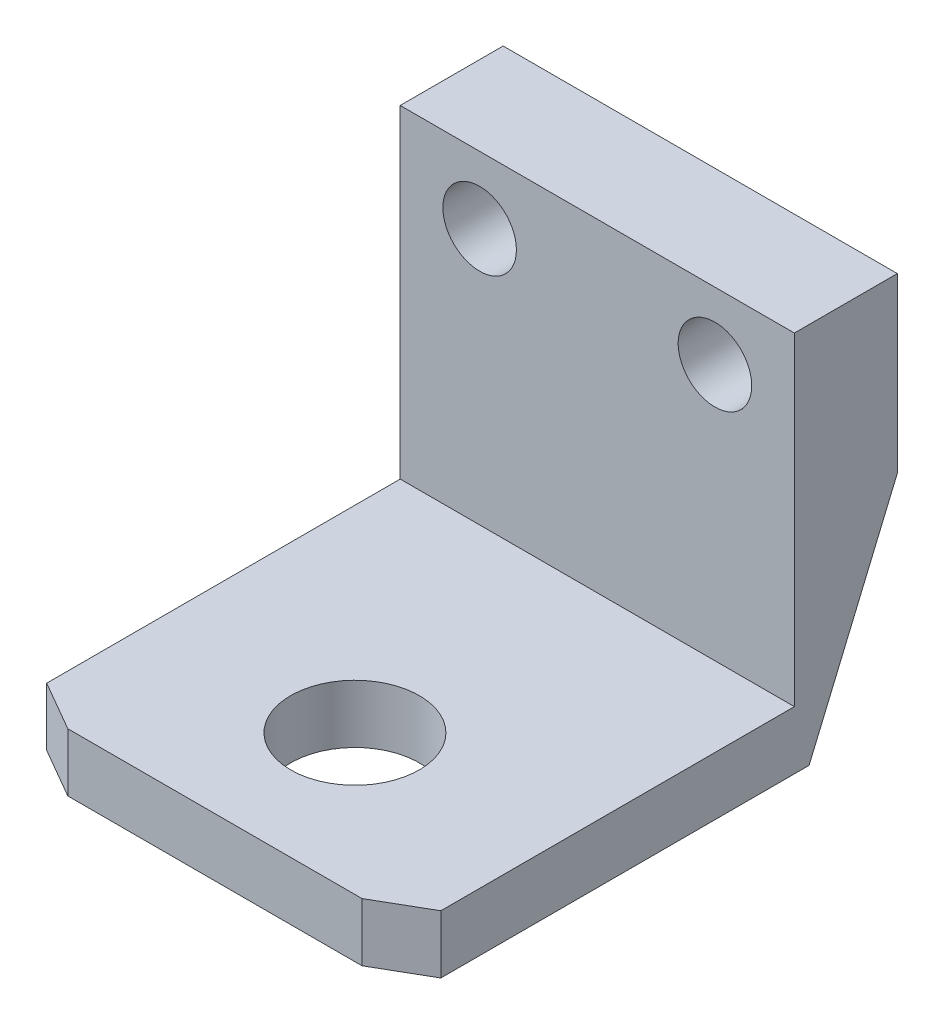
SolidWorks part; units mm, degrees
ref_plane "Front Plane" through (0, 0, 0) normal (0, 0, 1) x (1, 0, 0)
ref_plane "Top Plane" through (0, 0, 0) normal (0, 1, 0) x (1, 0, 0)
ref_plane "Right Plane" through (0, 0, 0) normal (1, 0, 0) x (0, 0, -1)
sketch "Sketch1" plane through (0, 0, 0) normal (0, 1, 0) x (1, 0, 0)
  line L0 (-27.051, 7.874) -> (-17.018, 7.874)
  line L1 (27.051, 7.874) -> (27.051, -7.874)
  line L2 (27.051, -7.874) -> (12.7, -16.1596)
  line L3 (12.7, -16.1596) -> (-12.7, -16.1596)
  line L4 (-12.7, -16.1596) -> (-27.051, -7.874)
  line L5 (-27.051, -7.874) -> (-27.051, 7.874)
  line L6 (-17.018, 7.874) -> (-17.018, 16.8604)
  line L7 (-17.018, 16.8604) -> (17.018, 16.8604)
  line L8 (17.018, 16.8604) -> (17.018, 7.874)
  line L9 (17.018, 7.874) -> (27.051, 7.874)
  line L10 (0, -55) -> (0, 55) construction
  line L11 (-27.051, 0) -> (27.051, 0) construction
  line L14 (-55, 0) -> (55, 0) construction
  point P2 (0, -16.1596)
  point P13 (0, 16.8604)
  point P14 (0, 0)
  dimension "D1" = 25.4
  dimension "D3" = 54.102
  dimension "D4" = 34.036
  dimension "D5" = 33.02
  dimension "D2" = 15.748
  dimension "D6" = 30
extrude "Boss-Extrude1" add sketch "Sketch1" along normal blind 5.0292 contours L0 L6 L7 L8 L9 L1 L2 L3 L4 L5
sketch "Sketch2" plane through (0, 0, 0) normal (0, 1, 0) x (1, 0, 0)
  line L0 (0, -55) -> (0, 55) construction
  line L1 (17.018, 25.7504) -> (-17.018, 25.7504)
  line L2 (17.018, 25.7504) -> (17.018, 16.8604)
  line L3 (17.018, 16.8604) -> (-17.018, 16.8604)
  line L4 (-17.018, 25.7504) -> (-17.018, 16.8604)
  line L5 (17.018, 25.7504) -> (-17.018, 16.8604) construction
  line L6 (17.018, 16.8604) -> (-17.018, 25.7504) construction
  point P0 (0, 21.3054)
  dimension "D1" = 8.89
extrude "Boss-Extrude2" add sketch "Sketch2" along normal blind 32.9692
sketch "Sketch3" plane through (17.018, 0, 0) normal (1, 0, 0) x (0, 0, -1)
  line L0 (25.7504, 32.9692) -> (25.7504, 0) construction
  line L1 (16.8604, 32.9692) -> (25.7504, 32.9692) construction
  line L2 (55, 0) -> (-55, 0) construction
  line L3 (25.7504, 18.034) -> (18.1304, 0)
  point P0 (25.7504, 18.034)
  point P5 (18.1304, 0)
  dimension "D1" = 14.9352
  dimension "D2" = 7.62
extrude "Cut-Extrude1" cut sketch "Sketch3" against normal through all and the other way through all
sketch "Sketch4" plane through (0, 0, -16.8604) normal (0, 0, 1) x (1, 0, 0)
  line L0 (-10.16, 27.178) -> (10.16, 27.178)
  line L1 (0, -18.1331) -> (0, 18.1331) construction
  line L2 (-17.018, 32.9692) -> (17.018, 32.9692) construction
  point P0 (-10.16, 27.178)
  point P1 (10.16, 27.178)
  point P2 (0, 27.178)
  dimension "D1" = 20.32
  dimension "D2" = 5.7912
hole_wizard "1/4 (0.25) Diameter Hole1" positions "Sketch5" profile "Sketch6" hole size "1/4" standard "ANSI Inch" end condition through all
sketch "Sketch5" plane through (0, 0, -16.8604) normal (0, 0, 1) x (1, 0, 0)
  point P0 (-10.16, 27.178)
  point P3 (10.16, 27.178)
sketch "Sketch6" plane through (-10.16, 27.178, -16.8604) normal (1, 0, 0) x (0, -1, 0)
  line L0 (0, 0) -> (0, 8.89)
  line L1 (0, 8.89) -> (3.175, 8.89)
  line L2 (3.175, 8.89) -> (3.175, 0)
  line L5 (3.175, 0) -> (0, 0)
  line L11 (0, -6.35) -> (0, 107.95) construction
  dimension "Thru Hole Dia." = 6.35
  dimension "Thru Hole Depth" = 8.89
sketch "Sketch7" plane through (0, 5.0292, 0) normal (0, 1, 0) x (1, 0, 0)
  line L0 (0, -18.1331) -> (0, 18.1331) construction
  line L1 (-27.051, -7.874) -> (-27.051, 7.874) construction
  circle A0 centre (0, -4.064) radius 5.5562
  point P0 (0, -4.064)
  point P5 (-27.051, -4.064)
  dimension "D1" = 11.1125
  dimension "D2" = 3.81
extrude "Cut-Extrude2" cut sketch "Sketch7" against normal through all contours A0
sketch "Sketch8" plane through (0, 5.0292, 0) normal (0, 1, 0) x (1, 0, 0)
  line L0 (27.051, 7.874) -> (27.051, -7.874) construction
  line L1 (-27.051, -7.874) -> (-27.051, 7.874) construction
  point P0 (23.241, -4.064)
  point P1 (-23.241, -4.064)
  dimension "D2" = 3.81
  dimension "D1" = 3.81
  dimension "D3" = 3.81
  dimension "D4" = 3.81
hole_wizard "#4-40 Tapped Hole1" positions "Sketch9" profile "Sketch10" tap size "#4-40" standard "ANSI Inch" end condition through all
sketch "Sketch9" plane through (0, 5.0292, 0) normal (0, 1, 0) x (1, 0, 0)
  point P0 (23.241, -4.064)
  point P3 (-23.241, -4.064)
sketch "Sketch10" plane through (23.241, 5.0292, 4.064) normal (1, 0, 0) x (0, 0, 1)
  line L0 (0, 0) -> (0, 5.0292)
  line L1 (0, 5.0292) -> (1.1303, 5.0292)
  line L2 (1.1303, 5.0292) -> (1.1303, 0)
  line L5 (1.1303, 0) -> (0, 0)
  line L11 (0, -6.35) -> (0, 107.95) construction
  dimension "Thru Tap Drill Dia." = 2.2606
  dimension "Thru Tap Drill Depth" = 5.0292
cosmetic thread "Hole Thread1" parameters "D2"=2.8448
cosmetic thread "Hole Thread2" parameters "D2"=2.8448
sketch "Sketch11" plane through (0, 5.0292, 0) normal (0, 1, 0) x (1, 0, 0)
  line L0 (17.018, 16.8604) -> (17.018, 7.874) construction
  line L1 (-27.051, 7.874) -> (-17.018, 7.874)
  line L2 (-27.051, 7.874) -> (-27.051, -16.1596)
  line L3 (-27.051, -16.1596) -> (-17.018, -16.1596)
  line L4 (-17.018, 7.874) -> (-17.018, -16.1596)
  line L5 (27.051, 7.874) -> (17.018, 7.874)
  line L6 (27.051, 7.874) -> (27.051, -16.1596)
  line L7 (27.051, -16.1596) -> (17.018, -16.1596)
  line L8 (17.018, 7.874) -> (17.018, -16.1596)
  line L9 (-17.018, 7.874) -> (-17.018, 16.8604) construction
  line L10 (12.7, -16.1596) -> (-12.7, -16.1596) construction
extrude "Cut-Extrude3" cut sketch "Sketch11" against normal through all
equation "\"angle\"= 30"
equation "\"D6@Sketch1\"=\"angle\""
equation "\"chamfer offset\"= 0.3in"
equation "\"D2@Sketch3\"=\"chamfer offset\""
equation "\"hole height\"= 0.228in"
equation "\"D2@Sketch4\"=\"hole height\""
equation "\"Large hole offset\"= 0.15in"
equation "\"D2@Sketch7\"=\"Large hole offset\""
equation "\"D1@Sketch8\"=\"Large hole offset\""
